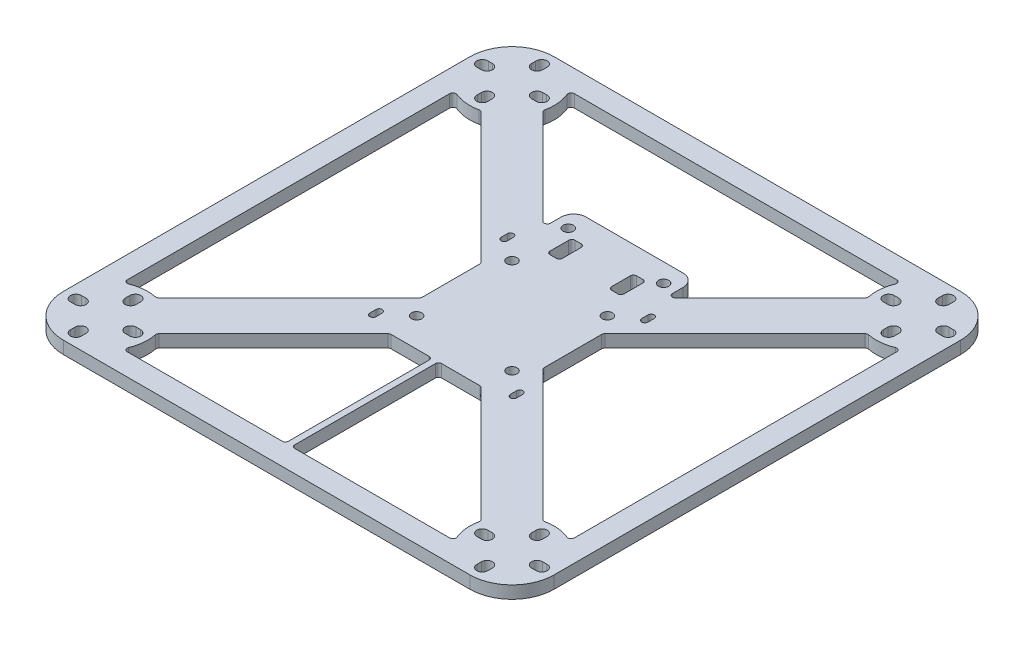
SolidWorks part; units mm, degrees
ref_plane "Front Plane" through (0, 0, 0) normal (0, 0, 1) x (1, 0, 0)
ref_plane "Top Plane" through (0, 0, 0) normal (0, 1, 0) x (1, 0, 0)
ref_plane "Right Plane" through (0, 0, 0) normal (1, 0, 0) x (0, 0, -1)
sketch "Sketch1" plane through (0, 0, 0) normal (0, 1, 0) x (1, 0, 0)
  line L0 (0, 78.5) -> (0, -78.5) construction
  line L1 (-78.5, 78.5) -> (78.5, 78.5)
  line L2 (-78.5, 78.5) -> (-78.5, -78.5)
  line L3 (-78.5, -78.5) -> (78.5, -78.5)
  line L4 (78.5, 78.5) -> (78.5, -78.5)
  line L5 (-78.5, 78.5) -> (78.5, -78.5) construction
  line L6 (-78.5, -78.5) -> (78.5, 78.5) construction
  line L7 (78.5, 0) -> (-78.5, 0) construction
  line L8 (-1, 65) -> (-1, 0) construction
  line L9 (-83.4497, 73.5503) -> (73.5503, -83.4497)
  line L10 (-73.5503, 83.4497) -> (83.4497, -73.5503)
  line L11 (-73.5503, -83.4497) -> (83.4497, 73.5503)
  line L12 (-83.4497, -73.5503) -> (73.5503, 83.4497)
  line L13 (-53.1678, 71.5) -> (53.1678, 71.5)
  line L14 (-53.1678, -71.5) -> (53.1678, -71.5)
  line L15 (71.5, -53.1678) -> (71.5, 53.1678)
  line L16 (-71.5, -53.1678) -> (-71.5, 53.1678)
  circle A0 centre (-65, 65) radius 13.5
  circle A1 centre (-65, 65) radius 64
  circle A2 centre (65, 65) radius 13.5
  circle A3 centre (-65, -65) radius 13.5
  circle A4 centre (65, -65) radius 13.5
  point P0 (0, 0)
  dimension "D1" = 27
  dimension "D2" = 128
  dimension "D3" = 2
  dimension "D4" = 14
  dimension "D5" = 7
extrude "Base shape" add sketch "Sketch1" along normal blind 4 contours L12 A3 L11 L9 | A4 L10 L11 L9 | L11 A2 L12 L10 | L9 A1 L10 A0 | A1 L9 L12 L10 | L12 L9 L11 L10 | L13 A1 L1 A0 | L13 A2 L1 A1 | A4 L4 A2 L15 | A4 L14 A3 L3 | L2 A3 L16 A1 | L2 A1 L16 A0 | A0 | A2 | A4 | A3 region at (-29.268, 0, -75.0845) region at (-75.0845, 0, -29.268) region at (27.4447, 0, -75.1014) region at (-37.8705, 0, -37.8705) region at (-75.1014, 0, 27.4447) region at (-12.3929, 0, -12.3929) region at (30.427, 0, -30.427) region at (0, 0, 0) region at (-30.427, 0, 30.427) region at (30.427, 0, 30.427) region at (75.0932, 0, 0) region at (0, 0, 75.0932)
sketch "Sketch2" plane through (0, 4, 0) normal (0, 1, 0) x (1, 0, 0)
  line L0 (-65, 74.5) -> (-65, 55.5) construction
  line L1 (-74.5, 65) -> (-55.5, 65) construction
  line L2 (0, 78.5) -> (0, -78.5) construction
  line L3 (-65, 78.5) -> (65, 78.5) construction
  line L4 (-65, -78.5) -> (65, -78.5) construction
  line L5 (-78.5, 0) -> (78.5, 0) construction
  line L6 (-78.5, 65) -> (-78.5, -65) construction
  line L7 (78.5, 65) -> (78.5, -65) construction
  line L8 (-66.75, 74.5) -> (-66.75, 73)
  line L9 (-63.25, 74.5) -> (-63.25, 73)
  line L10 (-74.5, 66.75) -> (-73, 66.75)
  line L11 (-74.5, 63.25) -> (-73, 63.25)
  line L12 (-66.75, 57) -> (-66.75, 55.5)
  line L13 (-63.25, 57) -> (-63.25, 55.5)
  line L14 (-57, 66.75) -> (-55.5, 66.75)
  line L15 (-57, 63.25) -> (-55.5, 63.25)
  line L16 (63.25, 57) -> (63.25, 55.5)
  line L17 (66.75, 57) -> (66.75, 55.5)
  line L18 (74.5, 63.25) -> (73, 63.25)
  line L19 (74.5, 66.75) -> (73, 66.75)
  line L20 (63.25, 74.5) -> (63.25, 73)
  line L21 (66.75, 74.5) -> (66.75, 73)
  line L22 (57, 66.75) -> (55.5, 66.75)
  line L23 (57, 63.25) -> (55.5, 63.25)
  line L24 (-66.75, -57) -> (-66.75, -55.5)
  line L25 (-63.25, -57) -> (-63.25, -55.5)
  line L26 (-57, -63.25) -> (-55.5, -63.25)
  line L27 (-57, -66.75) -> (-55.5, -66.75)
  line L28 (-74.5, -63.25) -> (-73, -63.25)
  line L29 (-74.5, -66.75) -> (-73, -66.75)
  line L30 (-63.25, -74.5) -> (-63.25, -73)
  line L31 (-66.75, -74.5) -> (-66.75, -73)
  line L32 (57, -63.25) -> (55.5, -63.25)
  line L33 (57, -66.75) -> (55.5, -66.75)
  line L34 (66.75, -74.5) -> (66.75, -73)
  line L35 (63.25, -74.5) -> (63.25, -73)
  line L36 (74.5, -66.75) -> (73, -66.75)
  line L37 (74.5, -63.25) -> (73, -63.25)
  line L38 (66.75, -57) -> (66.75, -55.5)
  line L39 (63.25, -57) -> (63.25, -55.5)
  circle A0 centre (-65, 65) radius 9.5
  circle A1 centre (-65, 65) radius 8
  circle A2 centre (-65, 74.5) radius 1.75
  circle A3 centre (-65, 55.5) radius 1.75
  circle A4 centre (-57, 65) radius 1.75
  circle A5 centre (-73, 65) radius 1.75
  circle A6 centre (-65, 73) radius 1.75
  circle A7 centre (-55.5, 65) radius 1.75
  circle A8 centre (-74.5, 65) radius 1.75
  circle A9 centre (-65, 57) radius 1.75
  circle A10 centre (65, 57) radius 1.75
  circle A11 centre (65, 55.5) radius 1.75
  circle A12 centre (73, 65) radius 1.75
  circle A13 centre (74.5, 65) radius 1.75
  circle A14 centre (65, 73) radius 1.75
  circle A15 centre (65, 74.5) radius 1.75
  circle A16 centre (57, 65) radius 1.75
  circle A17 centre (55.5, 65) radius 1.75
  circle A18 centre (-65, -57) radius 1.75
  circle A19 centre (-65, -55.5) radius 1.75
  circle A20 centre (-57, -65) radius 1.75
  circle A21 centre (-55.5, -65) radius 1.75
  circle A22 centre (-74.5, -65) radius 1.75
  circle A23 centre (-73, -65) radius 1.75
  circle A24 centre (-65, -74.5) radius 1.75
  circle A25 centre (-65, -73) radius 1.75
  circle A26 centre (55.5, -65) radius 1.75
  circle A27 centre (57, -65) radius 1.75
  circle A28 centre (65, -74.5) radius 1.75
  circle A29 centre (65, -73) radius 1.75
  circle A30 centre (74.5, -65) radius 1.75
  circle A31 centre (73, -65) radius 1.75
  circle A32 centre (65, -55.5) radius 1.75
  circle A33 centre (65, -57) radius 1.75
  dimension "D1" = 19
  dimension "D2" = 16
  dimension "D3" = 3.5
extrude "Motor mounting holes" cut sketch "Sketch2" against normal up to next contours A27 A26 | A26 A27 | A27 A26 | A27 L32 A26 | A27 A26 L33 | A29 A28 | A28 A29 | A28 A29 | A29 L35 A28 | A29 A28 L34 | A31 A30 | A30 A31 | A31 A30 | A31 A30 L37 | A31 L36 A30 | A33 A32 | A32 A33 | A33 A32 | A33 A32 L39 | A33 L38 A32 | A17 A16 | A17 A16 | A16 A17 | L22 A17 A16 | A16 A17 L23 | A11 A10 | A11 A10 | A10 A11 | L16 A11 A10 | A10 A11 L17 | A12 A13 | A13 A12 | A13 A12 | A12 A13 L19 | L18 A13 A12 | A14 A15 | A15 A14 | A15 A14 | A14 A15 L20 | L21 A15 A14 | A8 A5 L10 A0 | A8 A0 L11 A5 | A6 A2 A0 L8 | A6 L9 A0 A2 | A7 A4 L15 A0 | A7 A0 L14 A4 | A9 L12 A0 A3 | A9 A3 A0 L13 | A19 A18 | A19 A18 | A18 A19 | A18 A19 L24 | L25 A19 A18 | A22 A23 | A23 A22 | A23 A22 | A22 A23 L28 | L29 A23 A22 | A21 A20 | A21 A20 | A20 A21 | A20 A21 L26 | L27 A21 A20 | A24 A25 | A25 A24 | A25 A24 | A24 A25 L31 | L30 A25 A24 | A8 | A5 | A2 | A6 | A4 | A7 | A9 | A3 region at (-66.6996, 4, -73.7469) region at (-73.7469, 4, -66.6996) region at (-63.3004, 4, -73.7469) region at (-56.2531, 4, -66.6996) region at (-73.7469, 4, -63.3004) region at (-66.6996, 4, -56.2531) region at (-56.2531, 4, -63.3004) region at (-63.3004, 4, -56.2531) region at (63.3002, 4, -56.25) region at (65, 4, -57.6692) region at (65, 4, -54.8308) region at (66.6998, 4, -56.25) region at (65, 4, -56.25) region at (75.1692, 4, -65) region at (73.75, 4, -63.3002) region at (72.3308, 4, -65) region at (73.75, 4, -65) region at (73.75, 4, -66.6998) region at (63.3002, 4, -73.75) region at (65, 4, -75.1692) region at (65, 4, -72.3308) region at (66.6998, 4, -73.75) region at (65, 4, -73.75) region at (56.25, 4, -66.6998) region at (57.6692, 4, -65) region at (54.8308, 4, -65) region at (56.25, 4, -65) region at (56.25, 4, -63.3002) region at (-65, 4, 57.6692) region at (-66.6998, 4, 56.25) region at (-65, 4, 54.8308) region at (-63.3002, 4, 56.25) region at (-65, 4, 56.25) region at (-57.6692, 4, 65) region at (-56.25, 4, 63.3002) region at (-54.8308, 4, 65) region at (-56.25, 4, 66.6998) region at (-56.25, 4, 65) region at (-75.1692, 4, 65) region at (-73.75, 4, 63.3002) region at (-72.3308, 4, 65) region at (-73.75, 4, 66.6998) region at (-73.75, 4, 65) region at (-63.3002, 4, 73.75) region at (-65, 4, 75.1692) region at (-65, 4, 72.3308) region at (-66.6998, 4, 73.75) region at (-65, 4, 73.75) region at (56.25, 4, 63.3002) region at (57.6692, 4, 65) region at (54.8308, 4, 65) region at (56.25, 4, 65) region at (56.25, 4, 66.6998) region at (66.6998, 4, 73.75) region at (65, 4, 75.1692) region at (65, 4, 72.3308) region at (63.3002, 4, 73.75) region at (65, 4, 73.75) region at (75.1692, 4, 65) region at (73.75, 4, 66.6998)
sketch "Sketch5" plane through (0, 0, 0) normal (0, -1, 0) x (1, 0, 0)
  line L3 (-19.5, 10.25) -> (19.5, 10.25)
  line L4 (-19.5, 10.25) -> (-19.5, -10.25)
  line L7 (-19.5, -10.25) -> (19.5, -10.25)
  line L8 (19.5, 10.25) -> (19.5, -10.25)
  line L16 (-15.5, -39.2) -> (15.5, -39.2)
  line L17 (19.5, -35.2) -> (19.5, -10.25)
  line L18 (19.5, -10.25) -> (17.5, -10.25)
  line L19 (17.5, -10.25) -> (17.5, 10.25)
  line L20 (17.5, 10.25) -> (19.5, 10.25)
  line L21 (19.5, 10.25) -> (19.5, 24.5)
  line L22 (19.5, 24.5) -> (-19.5, 24.5)
  line L23 (-19.5, 24.5) -> (-19.5, 10.25)
  line L24 (-19.5, 10.25) -> (-17.5, 10.25)
  line L25 (-17.5, 10.25) -> (-17.5, -10.25)
  line L26 (-17.5, -10.25) -> (-19.5, -10.25)
  line L27 (-19.5, -10.25) -> (-19.5, -35.2)
  line L28 (-15.5, -39.2) -> (15.5, -39.2)
  line L29 (19.5, -35.2) -> (19.5, -10.25)
  line L30 (19.5, -10.25) -> (17.5, -10.25)
  line L31 (17.5, -10.25) -> (17.5, 10.25)
  line L32 (17.5, 10.25) -> (19.5, 10.25)
  line L33 (19.5, 10.25) -> (19.5, 24.5)
  line L34 (19.5, 24.5) -> (-19.5, 24.5)
  line L35 (-19.5, 24.5) -> (-19.5, 10.25)
  line L36 (-19.5, 10.25) -> (-17.5, 10.25)
  line L37 (-17.5, 10.25) -> (-17.5, -10.25)
  line L38 (-17.5, -10.25) -> (-19.5, -10.25)
  line L39 (-19.5, -10.25) -> (-19.5, -35.2)
  arc A2 (15.5, -39.2) -> (19.5, -35.2) centre (15.5, -35.2) ccw
  arc A3 (-19.5, -35.2) -> (-15.5, -39.2) centre (-15.5, -35.2) ccw
  arc A4 (15.5, -39.2) -> (19.5, -35.2) centre (15.5, -35.2) ccw
  arc A5 (-19.5, -35.2) -> (-15.5, -39.2) centre (-15.5, -35.2) ccw
  dimension "D1" = 0
extrude "OSD cover" add sketch "Sketch5" against normal up to surface (4 mm away) contours L34 L35 L3 L33 | L3 L37 L7 L31 | L37 L3 L4 L7 | L31 L7 L8 L3 | L39 A5 L28 A4 L29 L7 region at (0, 0, 17.375) region at (-18.5, 0, 0) region at (0, 0, 0) region at (0, 0, -24.6419) region at (18.5, 0, 0) up to face at (65, 4, 73.75)
sketch "Sketch7" plane through (0, 4, 0) normal (0, 1, 0) x (1, 0, 0)
  line L0 (18, 23) -> (-18, 23) construction
  line L1 (-8.85, 23) -> (-10.85, 23)
  line L2 (-7.85, 24) -> (-7.85, 30)
  line L3 (-8.85, 31) -> (-10.85, 31)
  line L4 (-11.85, 24) -> (-11.85, 30)
  line L5 (-7.85, 39.2) -> (-7.85, 23) construction
  line L6 (0, -24.5) -> (0, 39.2) construction
  line L10 (7.85, 39.2) -> (-4.95, 39.2) construction
  line L11 (8.85, 31) -> (10.85, 31)
  line L12 (11.85, 24) -> (11.85, 30)
  line L13 (8.85, 23) -> (10.85, 23)
  line L14 (7.85, 24) -> (7.85, 30)
  line L15 (14.6005, -24.5) -> (-14.6005, -24.5) construction
  circle A0 centre (-15.25, -15.25) radius 1.65 construction
  circle A1 centre (-15.25, 15.25) radius 1.65 construction
  circle A2 centre (-15.25, 33.25) radius 1.65 construction
  circle A3 centre (15.25, 33.25) radius 1.65 construction
  circle A4 centre (15.25, 15.25) radius 1.65 construction
  circle A5 centre (15.25, -15.25) radius 1.65 construction
  circle A6 centre (-15.25, -15.25) radius 1.65
  circle A7 centre (-15.25, 15.25) radius 1.65
  circle A8 centre (-15.25, 33.25) radius 1.65
  circle A9 centre (15.25, 33.25) radius 1.65
  circle A10 centre (15.25, 15.25) radius 1.65
  circle A11 centre (15.25, -15.25) radius 1.65
  arc A12 (8.85, 23) -> (7.85, 24) centre (8.85, 24) cw
  arc A13 (11.85, 24) -> (10.85, 23) centre (10.85, 24) cw
  arc A14 (10.85, 31) -> (11.85, 30) centre (10.85, 30) cw
  arc A15 (8.85, 31) -> (7.85, 30) centre (8.85, 30) ccw
  arc A16 (-10.85, 23) -> (-11.85, 24) centre (-10.85, 24) cw
  arc A17 (-8.85, 23) -> (-7.85, 24) centre (-8.85, 24) ccw
  arc A18 (-7.85, 30) -> (-8.85, 31) centre (-8.85, 30) ccw
  arc A19 (-10.85, 31) -> (-11.85, 30) centre (-10.85, 30) ccw
  point P29 (0, 0)
  point P40 (7.85, 23)
  point P43 (11.85, 23)
  point P46 (11.85, 31)
  point P49 (7.85, 31)
  point P52 (-11.85, 23)
  point P55 (-7.85, 23)
  point P58 (-7.85, 31)
  point P61 (-11.85, 31)
  dimension "D2" = 8
  dimension "D3" = 1
  dimension "D1" = 4
extrude "Main holes" cut sketch "Sketch7" against normal up to next contours A11 | A10 | A9 | A8 | A7 | A6 | L3 A19 L4 A16 L1 A17 L2 A18 | L11 A14 L12 A13 L13 A12 L14 A15
sketch "Sketch8" plane through (0, 0, 0) normal (0, -1, 0) x (1, 0, 0)
  line L0 (0, 78.5) -> (0, -71.5) construction
  line L1 (-65, 78.5) -> (65, 78.5) construction
  line L2 (-53.1678, -71.5) -> (53.1678, -71.5) construction
  line L4 (-1, 24.5) -> (1, 24.5)
  line L5 (-1, 24.5) -> (-1, 71.5)
  line L6 (-1, 71.5) -> (1, 71.5)
  line L7 (1, 24.5) -> (1, 71.5)
  line L8 (-53.1678, 71.5) -> (53.1678, 71.5) construction
  line L9 (0, 71.5) -> (0, 24.5) construction
  line L10 (-19.5, 24.5) -> (19.5, 24.5) construction
  point P10 (-1, 25.576)
  point P16 (0, 0)
  dimension "D1" = 2
extrude "VTX wire support" add sketch "Sketch8" against normal up to surface (4 mm away) up to face at (9.85, 4, -27)
sketch "Sketch9" plane through (0, 0, 0) normal (0, -1, 0) x (1, 0, 0)
  line L0 (22.5, 23) -> (22.5, 19) construction
  line L1 (-18, 23) -> (18, 23) construction
  line L2 (21.5, 19) -> (23.5, 19)
  line L3 (21.5, 19) -> (21.5, 23)
  line L4 (21.5, 23) -> (23.5, 23)
  line L5 (23.5, 19) -> (23.5, 23)
  line L6 (-21.5, 19) -> (-23.5, 19)
  line L7 (-21.5, 19) -> (-21.5, 23)
  line L8 (19.5, 24.5) -> (19.5, -35.2) construction
  line L9 (-21.5, 23) -> (-23.5, 23)
  line L10 (-23.5, 19) -> (-23.5, 23)
  line L11 (0, 78.5) -> (0, -78.5) construction
  line L12 (-65, 78.5) -> (65, 78.5) construction
  line L13 (-65, -78.5) -> (65, -78.5) construction
  line L14 (-78.5, 0) -> (78.5, 0) construction
  line L15 (-78.5, -65) -> (-78.5, 65) construction
  line L16 (78.5, -65) -> (78.5, 65) construction
  line L17 (21.5, -19) -> (23.5, -19)
  line L18 (21.5, -19) -> (21.5, -23)
  line L19 (21.5, -23) -> (23.5, -23)
  line L20 (23.5, -19) -> (23.5, -23)
  line L21 (-21.5, -19) -> (-23.5, -19)
  line L22 (-23.5, -19) -> (-23.5, -23)
  line L23 (-21.5, -23) -> (-23.5, -23)
  line L24 (-21.5, -19) -> (-21.5, -23)
  circle A0 centre (22.5, 22) radius 1
  circle A1 centre (22.5, 20) radius 1
  circle A2 centre (-22.5, 20) radius 1
  circle A3 centre (-22.5, 22) radius 1
  circle A4 centre (22.5, -20) radius 1
  circle A5 centre (22.5, -22) radius 1
  circle A6 centre (-22.5, -22) radius 1
  circle A7 centre (-22.5, -20) radius 1
  dimension "D3" = 4
  dimension "D1" = 2
  dimension "D2" = 2
extrude "ESC power wire cuts" cut sketch "Sketch9" against normal up to next contours A0 | A1 | A1 L5 A0 | A1 A0 L3 | A2 | A3 | A2 A3 L10 | L7 A3 A2 | A6 | A7 | A7 L22 A6 | A7 A6 L24 | A5 | A4 | A4 A5 L20 | L18 A5 A4 region at (22.5, 0, 20) region at (21.7234, 0, 21) region at (23.2766, 0, 21) region at (22.5, 0, 22) region at (-22.5, 0, 20) region at (-21.7234, 0, 21) region at (-23.2766, 0, 21) region at (-22.5, 0, 22) region at (22.5, 0, -20) region at (21.7234, 0, -21) region at (23.2766, 0, -21) region at (22.5, 0, -22) region at (-22.5, 0, -20) region at (-21.7234, 0, -21) region at (-23.2766, 0, -21) region at (-22.5, 0, -22)
fillet "Milling fillets" radius 1 28 edges at (53.1678, 2, -71.5) (51.8878, 2, -61.7873) (-53.1678, 2, -71.5) (-51.8878, 2, -61.7873) (-61.7873, 2, -51.8878) (-71.5, 2, -53.1678) (-71.5, 2, 53.1678) (-61.7873, 2, 51.8878) (-51.8878, 2, 61.7873) (-53.1678, 2, 71.5) (-1, 2, 71.5) (1, 2, 71.5) (51.8878, 2, 61.7873) (53.1678, 2, 71.5) (61.7873, 2, -51.8878) (71.5, 2, -53.1678) (61.7873, 2, 51.8878) (71.5, 2, 53.1678) (19.5, 2, -29.3995) (-19.5, 2, -29.3995) (-19.5, 2, 9.6005) (-19.5, 2, -9.6005) (19.5, 2, -9.6005) (19.5, 2, 9.6005) (1, 2, 24.5) (-14.6005, 2, 24.5) (-1, 2, 24.5) (14.6005, 2, 24.5)
sketch "Sketch3" plane through (0, 0, 0) normal (0, -1, 0) x (1, 0, 0)
  line L0 (0, -71.5) -> (0, -83.5) construction
  line L1 (-51.5836, -71.5) -> (51.5836, -71.5) construction
  line L2 (-65, -78.5) -> (65, -78.5) construction
  line L3 (0, -83.5) -> (-5, -78.5)
  line L4 (-5, -78.5) -> (5, -78.5)
  line L5 (0, -83.5) -> (5, -78.5)
  point P10 (0, -78.5)
  dimension "D1" = 5
  dimension "D2" = 45
extrude "TEST Forward arrow" [suppressed] add sketch "Sketch3" against normal up to surface (4 mm away) contours L4 L0 L5 | L0 L4 L3 up to face at (-22.5, 4, -21)
sketch "Sketch10" plane through (0, 4, 0) normal (0, 1, 0) x (1, 0, 0)
  line L0 (-65, -78.5) -> (65, -78.5) construction
  line L1 (29.5, 78.5) -> (78.5, 78.5)
  line L2 (29.5, 78.5) -> (29.5, -78.5)
  line L3 (29.5, -78.5) -> (78.5, -78.5)
  line L4 (78.5, 78.5) -> (78.5, -78.5)
  line L5 (78.5, 65) -> (78.5, -65) construction
  line L6 (19.5, 9.1863) -> (19.5, -9.1863) construction
  line L8 (-65, 78.5) -> (65, 78.5) construction
  dimension "D1" = 10
extrude "TEST print cut" [suppressed] cut sketch "Sketch10" against normal up to next
equation "\"MotorDiameter\"=27"
equation "\"D1@Sketch1\"=\"MotorDiameter\""
equation "\"PropDiameter\"=128"
equation "\"D2@Sketch1\"=\"PropDiameter\""
equation "\"PropDistance\"=2"
equation "\"D3@Sketch1\"=\"PropDistance\""
equation "\"ArmWidth\"=14"
equation "\"D4@Sketch1\"=\"ArmWidth\""
equation "\"FrameDepth\"=4"
equation "\"D1@Base shape\" = \"FrameDepth\""
equation "\"D5@Sketch1\"=\"ArmWidth\"/2"
equation "\"MotorHoleOuterDiameter\"=19"
equation "\"D1@Sketch2\"=\"MotorHoleOuterDiameter\""
equation "\"MotorHoleInnerDiameter\"=16"
equation "\"D2@Sketch2\"=\"MotorHoleInnerDiameter\""
equation "\"MotorHoleDiameter\"=3.5"
equation "\"D3@Sketch2\"=\"MotorHoleDiameter\""
